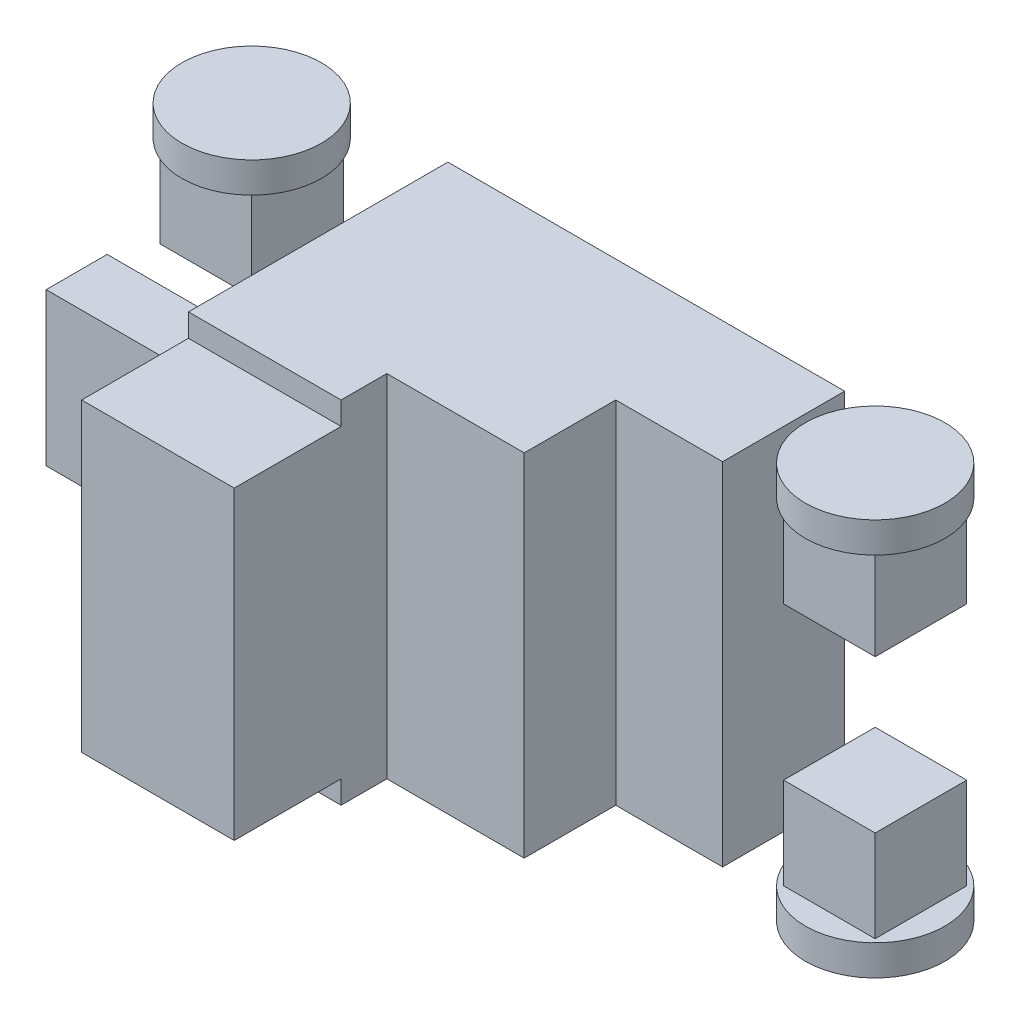
SolidWorks part; units mm, degrees
ref_plane "Front Plane" through (0, 0, 0) normal (1, 0, 0) x (0, 1, 0)
ref_plane "Top Plane" through (0, 0, 0) normal (0, 0, 1) x (0, 1, 0)
ref_plane "Right Plane" through (0, 0, 0) normal (0, 1, 0) x (-1, 0, 0)
sketch "Sketch1" plane through (0, 0, 0) normal (0, 1, 0) x (-1, 0, 0)
  line L0 (1375, 0) -> (-1375, 0) construction
  line L1 (-1207.2, 607.7677) -> (-1207.2, -150.9826) construction
  line L2 (1292.8, 510.1068) -> (1292.8, 21.8021) construction
  line L3 (650, 0) -> (650, 1200)
  line L4 (650, 1200) -> (150, 1200)
  line L5 (150, 1200) -> (150, 700)
  line L6 (150, 700) -> (-300, 700)
  line L7 (-300, 700) -> (-300, 400)
  line L8 (-300, 400) -> (-650, 400)
  line L9 (-650, 400) -> (-650, 0)
  line L10 (-650, 0) -> (650, 0)
  line L11 (-750, 606.7524) -> (-750, -249.5021) construction
  line L12 (-1507.2, 1276.6149) -> (-1507.2, -216.8938) construction
  line L13 (1492.8, 1256.9634) -> (1492.8, 400) construction
  line L15 (-1128.6, 378.6) -> (-828.6, 378.6)
  line L16 (-1128.6, 378.6) -> (-1128.6, 78.6)
  line L17 (-1128.6, 78.6) -> (-828.6, 78.6)
  line L18 (-828.6, 378.6) -> (-828.6, 78.6)
  line L19 (914.2, 378.6) -> (1214.2, 378.6)
  line L20 (914.2, 378.6) -> (914.2, 78.6)
  line L21 (914.2, 78.6) -> (1214.2, 78.6)
  line L22 (1214.2, 378.6) -> (1214.2, 78.6)
  line L23 (728.5312, 314.4591) -> (968.5312, 314.4591)
  line L24 (728.5312, 314.4591) -> (728.5312, 184.4591)
  line L25 (728.5312, 184.4591) -> (968.5312, 184.4591)
  line L26 (968.5312, 314.4591) -> (968.5312, 184.4591)
  line L27 (871.197, 495.0306) -> (1271.197, 495.0306)
  line L28 (871.197, 495.0306) -> (871.197, 695.0306)
  line L29 (871.197, 695.0306) -> (1271.197, 695.0306)
  line L30 (1271.197, 495.0306) -> (1271.197, 695.0306)
  circle A0 centre (-978.6, 228.6) radius 228.6
  circle A1 centre (1064.2, 228.6) radius 228.6
  point P19 (0, 0)
  point P38 (1271.197, 695.0306)
  dimension "D1" = 457.2
  dimension "D2" = 457.2
  dimension "D3" = 3000
  dimension "D4" = 1300
  dimension "D5" = 1200
  dimension "D6" = 500
  dimension "D7" = 500
  dimension "D8" = 400
  dimension "D9" = 350
  dimension "D10" = 100
  dimension "D11" = 300
  dimension "D12" = 200
  dimension "D13" = 300
  dimension "D14" = 300
  dimension "D15" = 150
  dimension "D16" = 150
  dimension "D17" = 150
  dimension "D18" = 150
  dimension "D19" = 130
  dimension "D20" = 240
  dimension "D21" = 200
  dimension "D22" = 400
ref_plane "Plane1" through (1500, 0, 0) normal (1, 0, 0) x (0, 1, 0)
sketch "Sketch3" plane through (1500, 0, 0) normal (1, 0, 0) x (0, 1, 0)
  line L0 (0, -797.2262) -> (0, 797.2262) construction
  line L1 (-237.5, 314.4591) -> (237.5, 314.4591)
  line L2 (-237.5, 314.4591) -> (-237.5, 184.4591)
  line L3 (-237.5, 184.4591) -> (237.5, 184.4591)
  line L4 (237.5, 314.4591) -> (237.5, 184.4591)
  line L5 (0, 314.4591) -> (0, 184.4591) construction
  line L6 (715, 0) -> (-715, 0) construction
  line L7 (650, 457.2) -> (550, 457.2)
  line L8 (650, 457.2) -> (650, 0)
  line L9 (650, 0) -> (550, 0)
  line L10 (550, 457.2) -> (550, 0)
  line L11 (0, 0) -> (0, 457.2) construction
  line L12 (550, 378.6) -> (250, 378.6)
  line L13 (550, 378.6) -> (550, 78.6)
  line L14 (550, 78.6) -> (250, 78.6)
  line L15 (250, 378.6) -> (250, 78.6)
  line L16 (0, 378.6) -> (0, 78.6) construction
  line L17 (-250, 378.6) -> (-250, 78.6)
  line L18 (-550, 78.6) -> (-250, 78.6)
  line L19 (-550, 378.6) -> (-550, 78.6)
  line L20 (-550, 378.6) -> (-250, 378.6)
  line L21 (-550, 457.2) -> (-550, 0)
  line L22 (-650, 0) -> (-550, 0)
  line L23 (-650, 457.2) -> (-650, 0)
  line L24 (-650, 457.2) -> (-550, 457.2)
  line L25 (-500, 850) -> (-500, 1200)
  line L26 (650, 850) -> (500, 850)
  line L27 (650, 850) -> (650, 1200)
  line L28 (650, 1200) -> (500, 1200)
  line L29 (500, 850) -> (500, 1200)
  line L30 (-650, 1200) -> (-500, 1200)
  line L31 (-650, 850) -> (-650, 1200)
  line L32 (-650, 850) -> (-500, 850)
  line L33 (0, 495.0306) -> (0, 695.0306) construction
  line L34 (-250, 695.0306) -> (250, 695.0306)
  line L35 (-250, 695.0306) -> (-250, 495.0306)
  line L36 (-250, 495.0306) -> (250, 495.0306)
  line L37 (250, 695.0306) -> (250, 495.0306)
  point P6 (0, 184.4591)
  point P50 (250, 733.592)
  point P52 (0, 0)
  point P53 (0, 0)
  point P56 (0, 0)
  dimension "D1" = 475
  dimension "D2" = 300
  dimension "D3" = 100
  dimension "D4" = 650
  dimension "D5" = 150
  dimension "D6" = 350
  dimension "D7" = 650
  dimension "D8" = 500
extrude "Boss-Extrude1" add sketch "Sketch1" along normal up to vertex (650 mm away) from vertex contours A0 up to point (1500, 650, 457.2) starting at point (1500, 550, 457.2)
extrude "Boss-Extrude2" add sketch "Sketch1<3>" against normal up to vertex (237.5 mm away) from vertex separate body contours L23 L26 L25 L24 up to point (1500, -237.5, 314.4591) starting at point (1500, 237.5, 314.4591)
sketch "Sketch1<3>" plane through (0, 0, 0) normal (0, 1, 0) x (-1, 0, 0) same geometry as "Sketch1"
extrude "Boss-Extrude3" add sketch "Sketch1<4>" along normal up to vertex (550 mm away) from vertex contours L15 L18 L17 L16 up to point (1500, 550, 378.6) starting at point (1500, 250, 378.6)
sketch "Sketch1<4>" plane through (0, 0, 0) normal (0, 1, 0) x (-1, 0, 0) same geometry as "Sketch1"
extrude "Boss-Extrude4" add sketch "Sketch1<5>" along normal mid plane 1150 separate body contours L4 L5 L6 L7 L8 L9 L10 L3
sketch "Sketch1<5>" plane through (0, 0, 0) normal (0, 1, 0) x (-1, 0, 0) same geometry as "Sketch1"
extrude "Cut-Extrude1" cut sketch "Sketch3" against normal up to surface (2150 mm away) contours L31 L32 L25 L30 | L28 L29 L26 L27 region at (1500, -575, 1025) up to face at (-650, 0, 600)
extrude "Boss-Extrude5" add sketch "Sketch1<6>" along normal up to vertex (550 mm away) from vertex separate body contours L19 L22 L21 L20 up to point (1500, 550, 378.6) starting at point (1500, 250, 378.6)
sketch "Sketch1<6>" plane through (0, 0, 0) normal (0, 1, 0) x (-1, 0, 0) same geometry as "Sketch1"
extrude "Boss-Extrude6" add sketch "Sketch1<7>" along normal up to vertex (650 mm away) from vertex contours A1 up to point (1500, 650, 457.2) starting at point (1500, 550, 457.2)
sketch "Sketch1<7>" plane through (0, 0, 0) normal (0, 1, 0) x (-1, 0, 0) same geometry as "Sketch1"
extrude "Boss-Extrude7" add sketch "Sketch1<8>" along normal up to vertex (250 mm away) from vertex separate body contours L29 L30 L27 L28 up to point (1500, 250, 695.0306) starting at point (1500, -250, 695.0306)
sketch "Sketch1<8>" plane through (0, 0, 0) normal (0, 1, 0) x (-1, 0, 0) same geometry as "Sketch1"
mirror "Mirror1" about plane through (0, 0, 0) normal (0, 1, 0) of bodies 103 107
